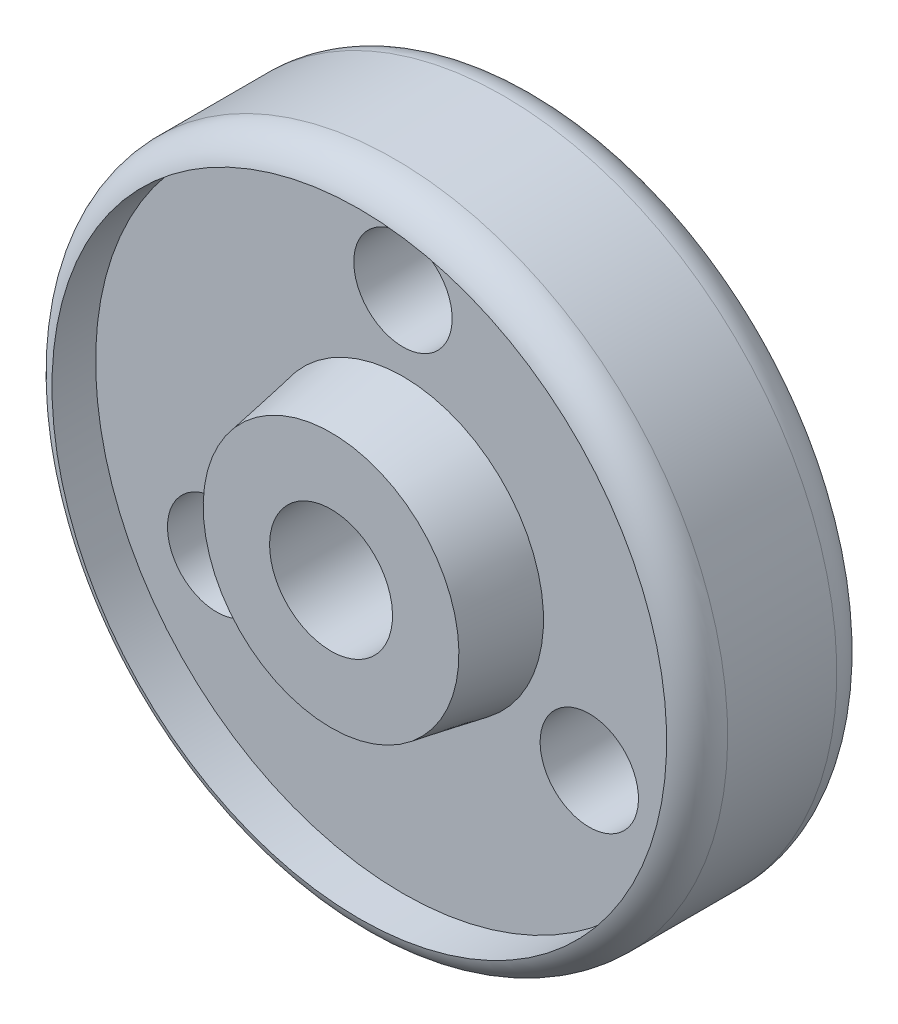
SolidWorks part; units mm, degrees
ref_plane "Front Plane" through (0, 0, 0) normal (0, 0, 1) x (1, 0, 0)
ref_plane "Top Plane" through (0, 0, 0) normal (0, 1, 0) x (1, 0, 0)
ref_plane "Right Plane" through (0, 0, 0) normal (1, 0, 0) x (0, 0, -1)
sketch "Sketch1" plane through (0, 0, 0) normal (1, 0, 0) x (0, 0, -1)
  line L0 (0, 0) -> (0, 70.5091) construction
  line L1 (-24.384, 12.7) -> (-24.384, 26.416)
  line L2 (-24.384, 12.7) -> (24.384, 12.7)
  line L3 (24.384, 12.7) -> (24.384, 26.416)
  line L4 (24.384, 26.416) -> (9.525, 29.036)
  line L5 (9.525, 29.036) -> (9.525, 63.5)
  line L6 (9.525, 63.5) -> (18.542, 63.5)
  line L7 (18.542, 63.5) -> (18.542, 68.834)
  line L8 (18.542, 68.834) -> (-18.542, 68.834)
  line L9 (0, 0) -> (85.6318, 0) construction
  line L10 (-24.384, 26.416) -> (-9.525, 29.036)
  line L11 (-9.525, 29.036) -> (-9.525, 63.5)
  line L12 (-9.525, 63.5) -> (-18.542, 63.5)
  line L13 (-18.542, 63.5) -> (-18.542, 68.834)
  point P6 (0, 12.7)
  point P18 (0, 68.834)
  dimension "D1" = 68.834
  dimension "D2" = 24.384
  dimension "D3" = 63.5
  dimension "D4" = 12.7
  dimension "D5" = 26.416
  dimension "D6" = 18.542
  dimension "D7" = 10
  dimension "D8" = 19.05
revolve "Revolve1" add sketch "Sketch1" angle 360 about L9
sketch "Sketch2" plane through (0, 0, 0) normal (0, 0, 1) x (1, 0, 0)
  line L0 (0, 0) -> (0, 44.45) construction
  circle A1 centre (0, 44.45) radius 10.16
  dimension "D2" = 20.32
  dimension "D1" = 44.45
extrude "Cut-Extrude2" cut sketch "Sketch2" against normal blind 254 and the other way blind 254
pattern_circular "CirPattern1" count 3 over 360 about axis through (0, 0, 0) along (0, 0, 1) of "Cut-Extrude2"
fillet "Fillet1" radius 7.62 2 edges at (0, -68.834, -18.542) (0, -68.834, 18.542)
